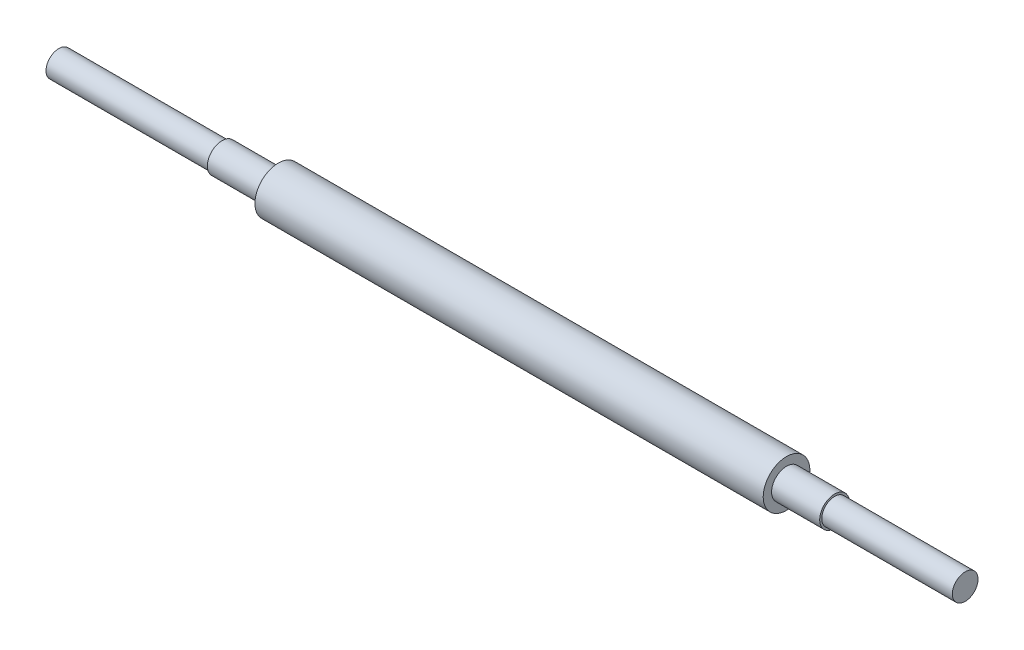
SolidWorks part; units mm, degrees
ref_plane "Front Plane" through (0, 0, 0) normal (0, 0, 1) x (1, 0, 0)
ref_plane "Top Plane" through (0, 0, 0) normal (0, 1, 0) x (1, 0, 0)
ref_plane "Right Plane" through (0, 0, 0) normal (1, 0, 0) x (0, 0, -1)
sketch "Sketch1" plane through (0, 0, 0) normal (0, 1, 0) x (1, 0, 0)
  line L0 (-78.6306, 0) -> (168.2085, 0) construction
  line L1 (-78.6306, 0) -> (-78.6306, 3.5)
  line L2 (-78.6306, 3.5) -> (-34.1806, 3.5)
  line L3 (-34.1806, 3.5) -> (-34.1806, 4)
  line L4 (-34.1806, 4) -> (-18.8815, 4)
  line L5 (-18.8815, 4) -> (-18.8815, 6.35)
  line L6 (-18.8815, 6.35) -> (119.5485, 6.35)
  line L7 (119.5485, 6.35) -> (119.5485, 4.064)
  line L8 (119.5485, 4.064) -> (132.6485, 4.064)
  line L9 (132.6485, 4.064) -> (132.6485, 3.5)
  line L10 (132.6485, 3.5) -> (168.2085, 3.5)
  line L11 (168.2085, 3.5) -> (168.2085, 0)
  line L12 (-78.6306, 0) -> (168.2085, 0)
  line L13 (-97.9506, 0) -> (194.5593, 0) construction
  point P15 (0, 0)
  dimension "D1" = 7
  dimension "D2" = 8
  dimension "D3" = 8.128
  dimension "D4" = 7
  dimension "D5" = 44.45
  dimension "D6" = 15.2991
  dimension "D7" = 13.1
  dimension "D8" = 35.56
  dimension "D9" = 138.43
  dimension "D10" = 6.35
revolve "Revolve1" add sketch "Sketch1" angle 360 about L13
